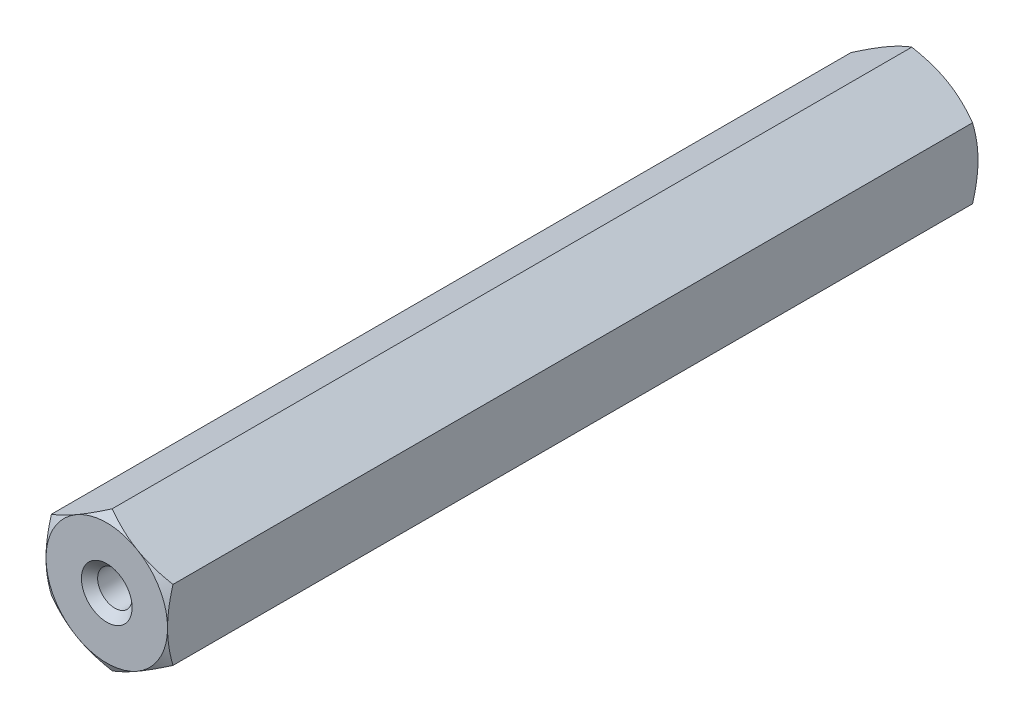
SolidWorks part; units mm, degrees
ref_plane "Front Plane" through (0, 0, 0) normal (0, 0, 1) x (1, 0, 0)
ref_plane "Top Plane" through (0, 0, 0) normal (0, 1, 0) x (1, 0, 0)
ref_plane "Right Plane" through (0, 0, 0) normal (1, 0, 0) x (0, 0, -1)
ref_axis "CL" through (0, 0, -34.925) along (0, 0, 1)
sketch "Sketch3" plane through (0, 0, 0) normal (1, 0, 0) x (0, 0, -1)
  line L0 (-31.75, 0) -> (31.75, 0) construction
  line L1 (0, 4.7625) -> (0, -4.7625) construction
  line L2 (-31.75, 1.7526) -> (-31.75, -1.7526) construction
  point P2 (22.225, 0)
  point P3 (-22.225, 0)
  dimension "Length" = 63.5
  dimension "Min Thread Length" = 9.525
  dimension "D1" = 9.525
  dimension "Thread Dia" = 3.5052
  dimension "Hex" = 9.525
sketch "Sketch1" plane through (0, 0, 0) normal (0, 0, 1) x (1, 0, 0)
  line L1 (0, 5.4993) -> (-4.7625, 2.7496)
  line L2 (-4.7625, 2.7496) -> (-4.7625, -2.7496)
  line L3 (-4.7625, -2.7496) -> (0, -5.4993)
  line L4 (0, -5.4993) -> (4.7625, -2.7496)
  line L5 (4.7625, -2.7496) -> (4.7625, 2.7496)
  line L6 (4.7625, 2.7496) -> (0, 5.4993)
  circle A0 centre (0, 0) radius 4.7625 construction
  circle A1 centre (0, 0) radius 1.7526
extrude "Extrude1" add sketch "Sketch1" along normal up to vertex (31.75 mm away) and the other way up to vertex (31.75 mm away) up to point (0, 0, 31.75) other way up to point (0, 0, -31.75)
sketch "Sketch11" plane through (0, 0, -31.75) normal (0, 0, -1) x (-1, 0, 0)
  circle A0 centre (0, 0) radius 1.7526 construction
  circle A1 centre (0, 0) radius 1.7526
curve "Helix/Spiral1" pitch 0.7937 height 64.2938 radius 1.7526 centre (0, 0, -31.75) axis (0, 0, 1) start towards (0, 1, 0) parameters "Pitch"=0.7937
sketch "Sketch12" plane through (0, 0, 0) normal (1, 0, 0) x (0, 0, -1)
  line L0 (32.4445, 1.7526) -> (31.75, 1.7526)
  line L1 (32.4445, 1.7526) -> (32.1469, 1.237)
  line L2 (32.1469, 1.237) -> (32.0477, 1.237)
  line L3 (32.0477, 1.237) -> (31.75, 1.7526)
  line L4 (32.0973, 1.237) -> (32.0973, 1.7526) construction
  line L5 (32.2957, 1.4948) -> (31.8988, 1.4948) construction
  dimension "D1" = 0.0992
  dimension "D2" = 0.3969
  dimension "D3" = 60
sweep "Sweep1" add profiles "Sketch12" path "Helix/Spiral1"
sketch "Sketch6" plane through (0, 0, -31.75) normal (0, 0, -1) x (-1, 0, 0)
  line L6 (0, 5.4993) -> (-4.7625, 2.7496)
  line L7 (-4.7625, 2.7496) -> (-4.7625, -2.7496)
  line L8 (-4.7625, -2.7496) -> (0, -5.4993)
  line L9 (0, -5.4993) -> (4.7625, -2.7496)
  line L10 (4.7625, -2.7496) -> (4.7625, 2.7496)
  line L11 (4.7625, 2.7496) -> (0, 5.4993)
  line L12 (0, 5.4993) -> (-4.7625, 2.7496)
  line L13 (-4.7625, 2.7496) -> (-4.7625, -2.7496)
  line L14 (-4.7625, -2.7496) -> (0, -5.4993)
  line L15 (0, -5.4993) -> (4.7625, -2.7496)
  line L16 (4.7625, -2.7496) -> (4.7625, 2.7496)
  line L17 (4.7625, 2.7496) -> (0, 5.4993)
  dimension "D1" = 0
extrude "Extrude2" cut sketch "Sketch6" along normal through all
sketch "Sketch7" plane through (0, 0, -31.75) normal (0, 0, -1) x (-1, 0, 0)
  circle A2 centre (0, 0) radius 1.8034
  circle A3 centre (0, 0) radius 1.8034
  dimension "D1" = 0.0508
extrude "Extrude3" cut sketch "Sketch7" against normal through all draft 43
sketch "Sketch8" plane through (0, 0, -31.75) normal (0, 0, -1) x (-1, 0, 0)
  circle A0 centre (0, 0) radius 4.7625 construction
  circle A1 centre (0, 0) radius 4.7625
extrude "Extrude4" cut sketch "Sketch8" against normal through all draft 60 flip side to cut
mirror "Mirror1" about plane through (0, 0, 0) normal (0, 0, 1) of "Extrude2", "Extrude3", "Extrude4"
sketch "Sketch9" plane through (0, 0, 0) normal (1, 0, 0) x (0, 0, -1)
  line L1 (-22.225, 1.8034) -> (22.225, 1.8034)
  line L2 (-22.225, 1.8034) -> (-22.225, 0)
  line L3 (-22.225, 0) -> (22.225, 0)
  line L4 (22.225, 1.8034) -> (22.225, 0)
  line L7 (-31.75, 0) -> (31.75, 0) construction
revolve "Revolve" add sketch "Sketch9" angle 360 about L0
sketch "Sketch10" plane through (0, 0, 0) normal (1, 0, 0) x (0, 0, -1)
  line L0 (31.75, 1.7526) -> (22.225, 1.7526)
  line L1 (-31.75, 1.7526) -> (-22.225, 1.7526)
  line L2 (22.225, 1.7526) -> (22.225, -1.7526)
  line L3 (-31.75, -1.8034) -> (-22.225, -1.8034)
  line L4 (-22.225, 1.7526) -> (-22.225, -1.8034)
  line L5 (22.225, -1.7526) -> (31.75, -1.7526)
sketch "Sketch13" plane through (0, 0, 31.75) normal (0, 0, 1) x (1, 0, 0)
  circle A0 centre (0, 0) radius 2.4953
extrude "Boss-Extrude1" add sketch "Sketch13" against normal up to surface (63.5 mm away) up to face at (-1.8034, 0, -31.75)
hole_wizard "#6-32 Tapped Hole1" positions "Sketch14" profile "Sketch15" tap size "#6-32" standard "ANSI Inch"
sketch "Sketch14" plane through (0, 0, 31.75) normal (0, 0, 1) x (1, 0, 0)
  point P0 (0, 0)
sketch "Sketch15" plane through (0, 0, 31.75) normal (1, 0, 0) x (0, -1, 0)
  line L0 (0, 0) -> (0, 11.7855)
  line L1 (0, 11.7855) -> (1.3525, 10.9728)
  line L2 (1.3525, 10.9728) -> (1.3525, 0.635)
  line L3 (1.3525, 0.635) -> (1.9875, 0)
  line L5 (1.9875, 0) -> (0, 0)
  line L6 (-1.3525, 0.635) -> (-1.9875, 0) construction
  line L10 (0, 11.7855) -> (-1.3525, 10.9728) construction
  line L11 (0, -6.35) -> (0, 107.95) construction
  dimension "Tap Drill Dia." = 2.7051
  dimension "Tap Drill Depth" = 10.9728
  dimension "Near C'Sink Dia." = 3.9751
  dimension "Near C'Sink Angle" = 90
  dimension "Drill Angle" = 118
hole_wizard "#6-32 Tapped Hole2" positions "Sketch16" profile "Sketch17" tap size "#6-32" standard "ANSI Inch"
sketch "Sketch16" plane through (0, 0, -31.75) normal (0, 0, -1) x (-1, 0, 0)
  point P0 (0, 0)
sketch "Sketch17" plane through (0, 0, -31.75) normal (1, 0, 0) x (0, 1, 0)
  line L0 (0, 0) -> (0, 11.7855)
  line L1 (0, 11.7855) -> (1.3525, 10.9728)
  line L2 (1.3525, 10.9728) -> (1.3525, 0.635)
  line L3 (1.3525, 0.635) -> (1.9875, 0)
  line L5 (1.9875, 0) -> (0, 0)
  line L6 (-1.3525, 0.635) -> (-1.9875, 0) construction
  line L10 (0, 11.7855) -> (-1.3525, 10.9728) construction
  line L11 (0, -6.35) -> (0, 107.95) construction
  dimension "Tap Drill Dia." = 2.7051
  dimension "Tap Drill Depth" = 10.9728
  dimension "Near C'Sink Dia." = 3.9751
  dimension "Near C'Sink Angle" = 90
  dimension "Drill Angle" = 118
equation "\"D1@Sketch3\" = \"Min Thread Length@Sketch3\""
equation "\"D3@Helix/Spiral1\" = \"Length@Sketch3\"+\"Pitch@Helix/Spiral1\""
equation "\"D1@Sketch12\" = \"Pitch@Helix/Spiral1\"*.125"
equation "\"D2@Sketch12\" = \"Pitch@Helix/Spiral1\"*.5"
